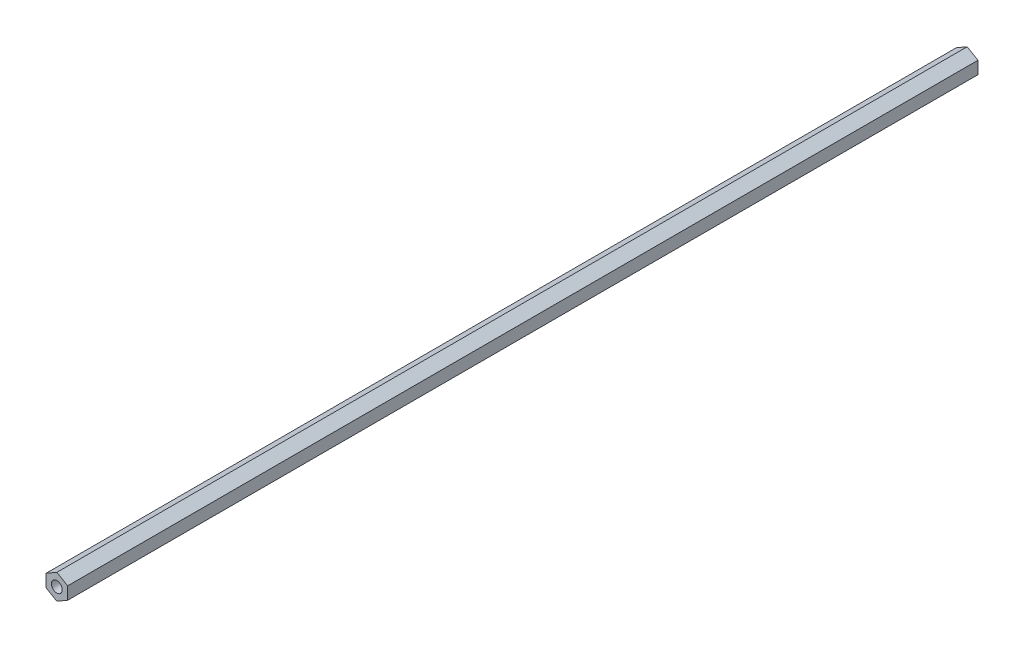
SolidWorks part; units mm, degrees
ref_plane "Front Plane" through (0, 0, 0) normal (0, 0, 1) x (1, 0, 0)
ref_plane "Top Plane" through (0, 0, 0) normal (0, 1, 0) x (1, 0, 0)
ref_plane "Right Plane" through (0, 0, 0) normal (1, 0, 0) x (0, 0, -1)
sketch "Sketch1" plane through (0, 0, 0) normal (0, 0, 1) x (1, 0, 0)
  line L1 (0, 7.3323) -> (-6.35, 3.6662) construction
  line L2 (-6.35, 3.6662) -> (-6.35, -3.6662) construction
  line L3 (-6.35, -3.6662) -> (0, -7.3323) construction
  line L4 (0, -7.3323) -> (6.35, -3.6662) construction
  line L5 (6.35, -3.6662) -> (6.35, 3.6662) construction
  line L6 (6.35, 3.6662) -> (0, 7.3323) construction
  circle A2 centre (0, 0) radius 6.35 construction
  dimension "Width" = 12.7
sketch "Sketch2" plane through (0, 0, 0) normal (1, 0, 0) x (0, 0, -1)
  line L0 (-266.7, 7.3323) -> (266.7, 7.3323) construction
  point P2 (0, 7.3323)
  point P3 (234.95, 7.3323)
  point P4 (-234.95, 7.3323)
  dimension "Length" = 533.4
  dimension "D2" = 31.75
  dimension "D1" = 31.75
sketch "Sketch3" plane through (0, 0, 0) normal (0, 0, 1) x (1, 0, 0)
  line L0 (-6.35, -3.6662) -> (0, -7.3323) construction
  line L1 (0, -7.3323) -> (6.35, -3.6662) construction
  line L2 (6.35, -3.6662) -> (6.35, 3.6662) construction
  line L3 (6.35, 3.6662) -> (0, 7.3323) construction
  line L4 (0, 7.3323) -> (-6.35, 3.6662) construction
  line L5 (-6.35, 3.6662) -> (-6.35, -3.6662) construction
  line L6 (-6.35, -3.6662) -> (0, -7.3323)
  line L7 (0, -7.3323) -> (6.35, -3.6662)
  line L8 (6.35, -3.6662) -> (6.35, 3.6662)
  line L9 (6.35, 3.6662) -> (0, 7.3323)
  line L10 (0, 7.3323) -> (-6.35, 3.6662)
  line L11 (-6.35, 3.6662) -> (-6.35, -3.6662)
extrude "Boss-Extrude2" add sketch "Sketch3" along normal up to vertex (266.7 mm away) and the other way up to vertex (266.7 mm away) up to point (0, 7.3323, 266.7) other way up to point (0, 7.3323, -266.7)
sketch "Sketch4" plane through (0, 0, 266.7) normal (0, 0, 1) x (1, 0, 0)
  point P0 (0, 0)
hole_wizard "1/4 (0.25) Diameter Hole1" positions "Sketch5" profile "Sketch6" hole size "1/4" standard "ANSI Inch"
sketch "Sketch5" plane through (0, 0, 266.7) normal (0, 0, 1) x (1, 0, 0)
  point P0 (0, 0)
sketch "Sketch6" plane through (0, 0, 266.7) normal (1, 0, 0) x (0, -1, 0)
  line L0 (0, 0) -> (0, 27.3077)
  line L1 (0, 27.3077) -> (3.175, 25.4)
  line L2 (3.175, 25.4) -> (3.175, 0)
  line L5 (3.175, 0) -> (0, 0)
  line L10 (0, 27.3077) -> (-3.175, 25.4) construction
  line L11 (0, -6.35) -> (0, 107.95) construction
  dimension "Hole Dia." = 6.35
  dimension "Hole Depth" = 25.4
  dimension "Drill Angle" = 118
hole_wizard "1/4 (0.25) Diameter Hole2" positions "Sketch7" profile "Sketch8" hole size "1/4" standard "ANSI Inch"
sketch "Sketch7" plane through (0, 0, -266.7) normal (0, 0, -1) x (-1, 0, 0)
  point P0 (0, 0)
sketch "Sketch8" plane through (0, 0, -266.7) normal (1, 0, 0) x (0, 1, 0)
  line L0 (0, 0) -> (0, 27.3077)
  line L1 (0, 27.3077) -> (3.175, 25.4)
  line L2 (3.175, 25.4) -> (3.175, 0)
  line L5 (3.175, 0) -> (0, 0)
  line L10 (0, 27.3077) -> (-3.175, 25.4) construction
  line L11 (0, -6.35) -> (0, 107.95) construction
  dimension "Hole Dia." = 6.35
  dimension "Hole Depth" = 25.4
  dimension "Drill Angle" = 118
equation "\"D2@Sketch2\" = \"D1@Sketch2\""
equation "\"D1@Sketch2\" = \"Width@Sketch1\" * 2.5"
